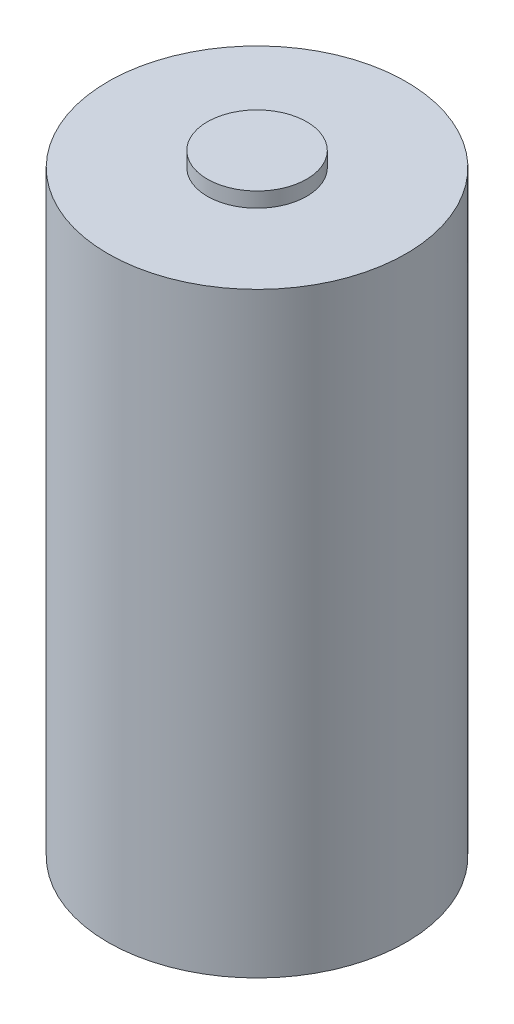
SolidWorks part; units mm, degrees
ref_plane "Front Plane" through (0, 0, 0) normal (0, 0, 1) x (1, 0, 0)
ref_plane "Top Plane" through (0, 0, 0) normal (0, 1, 0) x (1, 0, 0)
ref_plane "Right Plane" through (0, 0, 0) normal (1, 0, 0) x (0, 0, -1)
sketch "Sketch2" plane through (0, 0, 0) normal (0, 1, 0) x (1, 0, 0)
  circle A0 centre (0, 0) radius 3
  dimension "D1" = 6
extrude "Boss-Extrude1" add sketch "Sketch2" along normal blind 12
sketch "Sketch3" plane through (0, 12, 0) normal (0, 1, 0) x (1, 0, 0)
  circle A0 centre (0, 0) radius 1
  dimension "D1" = 2
extrude "Boss-Extrude2" add sketch "Sketch3" along normal blind 0.3
